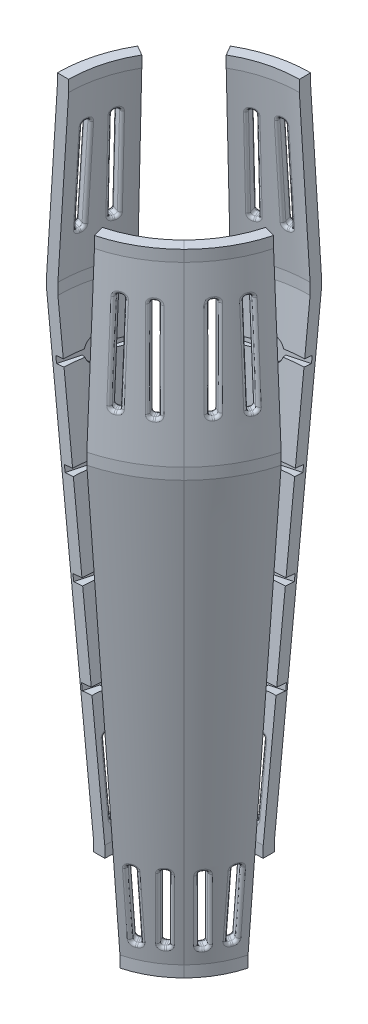
SolidWorks part; units mm, degrees
ref_plane "Front Plane" through (0, 0, 0) normal (0, 0, 1) x (1, 0, 0)
ref_plane "Top Plane" through (0, 0, 0) normal (0, 1, 0) x (1, 0, 0)
ref_plane "Right Plane" through (0, 0, 0) normal (1, 0, 0) x (0, 0, -1)
sketch "Sketch1" plane through (0, 0, 0) normal (0, 1, 0) x (1, 0, 0)
  line L0 (-28.2843, 28.2843) -> (-24.7487, 24.7487) construction
  line L1 (28.2843, 28.2843) -> (24.7487, 24.7487) construction
  line L2 (-24.7487, 24.7487) -> (0, 0) construction
  line L3 (24.7487, 24.7487) -> (0, 0) construction
  line L4 (0, 0) -> (0, 40) construction
  line L5 (-9.0587, -33.8074) -> (-10.3528, -38.637) construction
  line L6 (9.0587, -33.8074) -> (10.3528, -38.637)
  line L7 (0, 0) -> (9.0587, -33.8074) construction
  line L8 (0, 0) -> (-9.0587, -33.8074) construction
  line L9 (0, 0) -> (0, -40) construction
  line L10 (-24.7487, -24.7487) -> (-28.2843, -28.2843) construction
  line L11 (24.7487, -24.7487) -> (28.2843, -28.2843)
  line L12 (-24.7487, -24.7487) -> (0, 0) construction
  line L13 (0, 0) -> (24.7487, -24.7487) construction
  arc A0 (9.0587, -33.8074) -> (24.7487, -24.7487) centre (0, 0) ccw
  arc A1 (10.3528, -38.637) -> (28.2843, -28.2843) centre (0, 0) ccw
  arc A2 (-24.7487, -24.7487) -> (-9.0587, -33.8074) centre (0, 0) ccw construction
  arc A3 (-28.2843, -28.2843) -> (-10.3528, -38.637) centre (0, 0) ccw construction
  arc A4 (24.7487, 24.7487) -> (-24.7487, 24.7487) centre (0, 0) ccw construction
  arc A5 (28.2843, 28.2843) -> (-28.2843, 28.2843) centre (0, 0) ccw construction
  dimension "D1" = 70
  dimension "D2" = 5
  dimension "D3" = 45
  dimension "D4" = 45
  dimension "D5" = 15
  dimension "D6" = 15
  dimension "D7" = 30
  dimension "D8" = 30
ref_plane "Plane1" through (0, 210, 0) normal (0, 1, 0) x (1, 0, 0)
sketch "Sketch2" plane through (0, 210, 0) normal (0, 1, 0) x (1, 0, 0)
  line L0 (0, 0) -> (24.7487, -24.7487) construction
  line L1 (0, 0) -> (9.0587, -33.8074) construction
  line L2 (0, 0) -> (-9.0587, -33.8074) construction
  line L3 (-24.7487, -24.7487) -> (0, 0) construction
  line L4 (24.7487, 24.7487) -> (0, 0) construction
  line L5 (0, 0) -> (0, 40) construction
  line L6 (-24.7487, 24.7487) -> (0, 0) construction
  line L7 (0, 0) -> (24.7487, -24.7487) construction
  line L8 (0, 0) -> (9.0587, -33.8074) construction
  line L9 (0, 0) -> (-9.0587, -33.8074) construction
  line L10 (-24.7487, -24.7487) -> (0, 0) construction
  line L11 (24.7487, 24.7487) -> (0, 0) construction
  line L12 (0, 0) -> (0, 40) construction
  line L13 (-24.7487, 24.7487) -> (0, 0) construction
  line L14 (-42.9214, 42.9214) -> (-39.3858, 39.3858) construction
  line L15 (42.9214, 42.9214) -> (39.3858, 39.3858) construction
  line L16 (-39.3858, -39.3858) -> (-42.9214, -42.9214) construction
  line L17 (-14.4162, -53.8021) -> (-15.7103, -58.6317) construction
  line L18 (14.4162, -53.8021) -> (15.7103, -58.6317)
  line L19 (39.3858, -39.3858) -> (42.9214, -42.9214)
  arc A0 (-39.3858, -39.3858) -> (-14.4162, -53.8021) centre (0, 0) ccw construction
  arc A1 (-42.9214, -42.9214) -> (-15.7103, -58.6317) centre (0, 0) ccw construction
  arc A2 (39.3858, 39.3858) -> (-39.3858, 39.3858) centre (0, 0) ccw construction
  arc A3 (42.9214, 42.9214) -> (-42.9214, 42.9214) centre (0, 0) ccw construction
  arc A4 (14.4162, -53.8021) -> (39.3858, -39.3858) centre (0, 0) ccw
  arc A5 (15.7103, -58.6317) -> (42.9214, -42.9214) centre (0, 0) ccw
  dimension "D1" = 111.4
  dimension "D2" = 5
ref_plane "Plane2" through (0, 290, 0) normal (0, 1, 0) x (1, 0, 0)
sketch "Sketch3" plane through (0, 290, 0) normal (0, 1, 0) x (1, 0, 0)
  line L0 (-24.7487, -24.7487) -> (0, 0) construction
  line L1 (0, 0) -> (-9.0587, -33.8074) construction
  line L2 (0, 0) -> (9.0587, -33.8074) construction
  line L3 (0, 0) -> (24.7487, -24.7487) construction
  line L4 (24.7487, 24.7487) -> (0, 0) construction
  line L5 (0, 0) -> (0, 40) construction
  line L6 (-24.7487, 24.7487) -> (0, 0) construction
  line L7 (-24.7487, -24.7487) -> (0, 0) construction
  line L8 (0, 0) -> (-9.0587, -33.8074) construction
  line L9 (0, 0) -> (9.0587, -33.8074) construction
  line L10 (0, 0) -> (24.7487, -24.7487) construction
  line L11 (24.7487, 24.7487) -> (0, 0) construction
  line L12 (0, 0) -> (0, 40) construction
  line L13 (-24.7487, 24.7487) -> (0, 0) construction
  line L14 (-36.0271, 36.0271) -> (-39.5626, 39.5626) construction
  line L15 (39.5626, 39.5626) -> (36.0271, 36.0271) construction
  line L16 (-36.0271, -36.0271) -> (-39.5626, -39.5626) construction
  line L17 (-13.1868, -49.2139) -> (-14.4809, -54.0435) construction
  line L18 (13.1868, -49.2139) -> (14.4809, -54.0435)
  line L19 (36.0271, -36.0271) -> (39.5626, -39.5626)
  arc A0 (-36.0271, -36.0271) -> (-13.1868, -49.2139) centre (0, 0) ccw construction
  arc A1 (-39.5626, -39.5626) -> (-14.4809, -54.0435) centre (0, 0) ccw construction
  arc A2 (39.5626, 39.5626) -> (-39.5626, 39.5626) centre (0, 0) ccw construction
  arc A3 (36.0271, 36.0271) -> (-36.0271, 36.0271) centre (0, 0) ccw construction
  arc A4 (13.1868, -49.2139) -> (36.0271, -36.0271) centre (0, 0) ccw
  arc A5 (14.4809, -54.0435) -> (39.5626, -39.5626) centre (0, 0) ccw
  dimension "D1" = 101.9
  dimension "D2" = 5
extrude "Boss-Extrude1" add sketch "Sketch2" against normal blind 5
extrude "Boss-Extrude2" add sketch "Sketch1" along normal blind 5 separate body
loft "Loft4" add section face at (18.4306, 5, 31.9227) section face at (28.6042, 205, 49.544) connector at (10.3528, 5, 38.637) connector at (15.7103, 205, 58.6317)
extrude "Boss-Extrude3" add sketch "Sketch3" against normal blind 5 separate body
loft "Loft6" add section face at (28.6042, 210, 49.544) section face at (26.2697, 285, 45.5004) connector at (14.4162, 210, 53.8021) connector at (13.1868, 285, 49.2139)
ref_plane "Plane3" through (17.354, -3.1833, 30.058) normal (-0.4979, 0.0913, -0.8624) x (-0.8672, -0.0478, 0.4956)
sketch "Sketch9" plane through (17.354, -3.1833, 30.058) normal (-0.4979, 0.0913, -0.8624) x (-0.8672, -0.0478, 0.4956)
  line L0 (-24.4392, 208.1236) -> (-8.8517, 184.1082) construction
  line L1 (-8.8517, 184.1082) -> (4.36, 209.5082) construction
  line L2 (-24.4392, 208.1236) -> (4.36, 209.5082) construction
  line L7 (-3.6383, 185.8606) -> (9.0617, 186.4712)
  line L8 (-3.4942, 182.8641) -> (9.2058, 183.4747)
  line L29 (9.2058, 183.4747) -> (9.0617, 186.4712)
  line L31 (-14.065, 182.3558) -> (-26.765, 181.7453)
  line L32 (-26.765, 181.7453) -> (-26.9091, 184.7418)
  line L33 (-26.9091, 184.7418) -> (-14.2091, 185.3524)
  line L35 (-26.8371, 183.2435) -> (9.1337, 184.9729) construction
  line L36 (-9.4356, 7.6225) -> (8.6608, 8.4926) construction
  line L38 (-10.0396, 208.8159) -> (-0.3874, 8.0576) construction
  line L40 (-12.1441, 142.402) -> (-24.8441, 141.7914)
  line L41 (-24.8441, 141.7914) -> (-24.9882, 144.7879)
  line L42 (-24.9882, 144.7879) -> (-12.2882, 145.3985)
  line L43 (-1.7174, 145.9068) -> (10.9826, 146.5174)
  line L44 (11.1267, 143.5208) -> (10.9826, 146.5174)
  line L45 (-1.5733, 142.9102) -> (11.1267, 143.5208)
  line L46 (-10.2232, 102.4482) -> (-22.9232, 101.8376)
  line L47 (-22.9232, 101.8376) -> (-23.0672, 104.8341)
  line L48 (-23.0672, 104.8341) -> (-10.3672, 105.4447)
  line L49 (0.2036, 105.9529) -> (12.9036, 106.5635)
  line L50 (13.0476, 103.567) -> (12.9036, 106.5635)
  line L51 (0.3476, 102.9564) -> (13.0476, 103.567)
  line L52 (-8.3023, 62.4943) -> (-21.0023, 61.8837)
  line L53 (-21.0023, 61.8837) -> (-21.1463, 64.8803)
  line L54 (-21.1463, 64.8803) -> (-8.4463, 65.4909)
  line L55 (2.1245, 65.9991) -> (14.8245, 66.6097)
  line L56 (14.9685, 63.6131) -> (14.8245, 66.6097)
  line L57 (2.2685, 63.0025) -> (14.9685, 63.6131)
  arc A10 (-14.065, 182.3558) -> (-3.4942, 182.8641) centre (-8.8517, 184.1082) ccw
  arc A11 (-3.6383, 185.8606) -> (-14.2091, 185.3524) centre (-8.8517, 184.1082) ccw
  arc A12 (-1.7174, 145.9068) -> (-12.2882, 145.3985) centre (-6.9307, 144.1544) ccw
  arc A13 (-12.1441, 142.402) -> (-1.5733, 142.9102) centre (-6.9307, 144.1544) ccw
  arc A14 (0.2036, 105.9529) -> (-10.3672, 105.4447) centre (-5.0098, 104.2005) ccw
  arc A15 (-10.2232, 102.4482) -> (0.3476, 102.9564) centre (-5.0098, 104.2005) ccw
  arc A16 (2.1245, 65.9991) -> (-8.4463, 65.4909) centre (-3.0889, 64.2467) ccw
  arc A17 (-8.3023, 62.4943) -> (2.2685, 63.0025) centre (-3.0889, 64.2467) ccw
  dimension "D1" = 11
  dimension "D2" = 25.4
  dimension "D3" = 3
  dimension "D4" = 12.7
  dimension "D5" = 4
extrude "Cut-Extrude3" cut sketch "Sketch9" against normal blind 3 and the other way blind 3
ref_plane "Plane4" through (36.1255, 5.8578, 62.5712) normal (0.4984, 0.0808, 0.8632) x (0.8669, -0.0372, -0.497)
sketch "Sketch10" plane through (36.1255, 5.8578, 62.5712) normal (0.4984, 0.0808, 0.8632) x (0.8669, -0.0372, -0.497)
  line L0 (-2.8039, 264.8198) -> (-0.4945, 221.8672)
  line L9 (-0.4945, 221.8672) -> (-3.6695, 221.8672)
  line L10 (-3.6695, 221.8672) -> (-5.9789, 264.8198)
  line L11 (-5.9789, 264.8198) -> (-2.8039, 264.8198)
  line L16 (6.7522, 205.3608) -> (2.7183, 280.388) construction
  line L17 (-13.8045, 264.8198) -> (-16.9795, 264.8198)
  line L18 (-16.9795, 264.8198) -> (-16.0778, 221.8672)
  line L19 (-16.0778, 221.8672) -> (-12.9028, 221.8672)
  line L20 (-12.9028, 221.8672) -> (-13.8045, 264.8198)
  line L21 (-22.0601, 204.2841) -> (-23.637, 279.4031) construction
  ellipse E0 centre (-10.6079, 283.8698) end of major axis (-61.5224, 281.9671) minor radius 4.1173 (-23.637, 279.4031) -> (2.7183, 280.388) ccw construction
  ellipse E1 centre (-7.8163, 209.1672) end of major axis (-63.4775, 207.0872) minor radius 4.5012 (-22.0601, 204.2841) -> (6.7522, 205.3608) ccw construction
  point P26 (0, 0)
  point P27 (-14.2038, 242.0576)
  dimension "D1" = 19.05
  dimension "D2" = 12.7
  dimension "D3" = 3.175
  dimension "D4" = 6.35
  dimension "D5" = 6.35
  dimension "D6" = 6.35
  dimension "D7" = 6.35
  dimension "D8" = 19.05
  dimension "D9" = 12.7
  dimension "D10" = 3.175
extrude "Cut-Extrude4" cut sketch "Sketch10" against normal through all both and the other way through all
sketch "Sketch11" plane through (17.354, -3.1833, 30.058) normal (-0.4979, 0.0913, -0.8624) x (-0.8672, -0.0478, 0.4956)
  line L0 (-9.1835, 46.8021) -> (-6.8138, 15.1334)
  line L1 (-6.8138, 15.1334) -> (-3.6388, 15.1334)
  line L2 (-3.6388, 15.1334) -> (-6.0085, 46.8021)
  line L3 (-6.0085, 46.8021) -> (-9.1835, 46.8021)
  line L4 (1.4887, 46.8834) -> (2.168, 15.1334)
  line L5 (2.168, 15.1334) -> (5.343, 15.1334)
  line L6 (5.343, 15.1334) -> (4.6637, 46.8834)
  line L7 (4.6637, 46.8834) -> (1.4887, 46.8834)
  line L8 (-9.4356, 7.6225) -> (-13.5229, 62.2433) construction
  line L9 (8.6608, 8.4926) -> (7.4892, 63.2535) construction
  ellipse E0 centre (-0.2391, 4.9734) end of major axis (-35.1987, 3.2925) minor radius 3.1967 (8.6608, 8.4926) -> (-9.4356, 7.6225) ccw construction
  point P12 (0, 0)
  point P13 (5.3348, 15.0754)
  point P14 (-3.5472, 14.0207)
  point P15 (2.185, 14.0149)
  dimension "D1" = 3.175
  dimension "D2" = 3.175
  dimension "D3" = 3.175
  dimension "D4" = 3.175
  dimension "D5" = 3.175
  dimension "D6" = 31.75
  dimension "D7" = 10.16
  dimension "D8" = 10.16
extrude "Cut-Extrude5" cut sketch "Sketch11" along normal through all and the other way through all
fillet "Fillet1" radius 1.27 48 edges at (21.7557, 227.381, 50.0776) (21.0372, 270.263, 47.427) (23.5376, 270.6684, 51.7569) (24.2581, 227.7867, 54.4109) (32.5129, 226.9182, 43.8997) (35.0146, 227.3239, 48.2335) (32.4614, 227.1926, 46.9883) (21.5359, 227.6271, 52.8642) (20.8218, 270.5099, 50.2215) (23.7339, 270.4176, 48.9199) (24.4601, 227.5368, 51.5835) (30.5744, 269.8527, 41.9498) (30.5153, 270.1258, 45.0253) (33.0741, 270.2581, 46.2802) (33.106, 269.9814, 43.1668) (35.04, 227.0462, 45.109) (13.8261, 11.7497, 32.9125) (16.3207, 11.2924, 37.2312) (17.1841, 42.8788, 40.4192) (14.6861, 43.3368, 36.0945) (23.9503, 43.7664, 30.7952) (26.4467, 43.3083, 35.121) (24.1175, 11.7219, 32.7793) (21.6246, 12.1794, 28.4595) (17.4028, 43.1679, 37.6195) (16.5308, 11.583, 34.4167) (13.5899, 11.4655, 35.6657) (14.444, 43.0537, 38.8374) (21.5676, 11.8605, 31.5406) (23.9052, 43.4454, 33.897) (26.4548, 43.6346, 31.9704) (24.1351, 12.0464, 29.6449)
pattern_circular "CirPattern8" count 2 over 330 about axis through (0, 290, 0) along (0, -1, 0) of bodies 124 120
pattern_circular "CirPattern9" count 2 over 165 about axis through (0, 290, 0) along (0, -1, 0) of bodies 121
pattern_circular "CirPattern10" count 2 over 225 about axis through (0, 290, 0) along (0, -1, 0) of bodies 121
